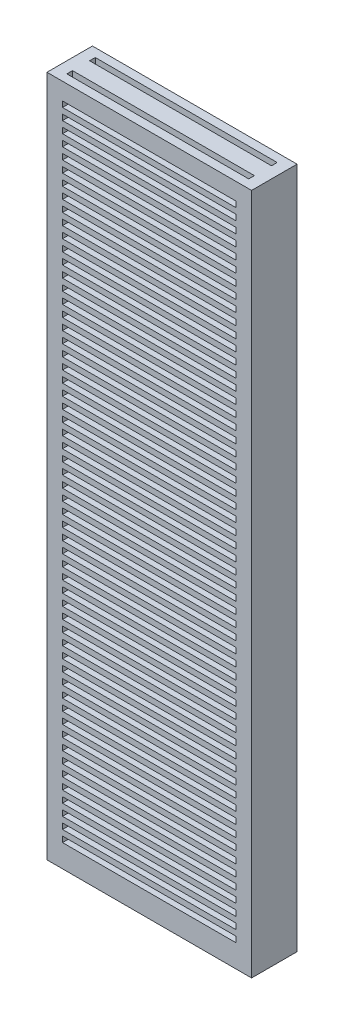
SolidWorks part; units mm, degrees
ref_plane "Front Plane" through (0, 0, 0) normal (0, 0, 1) x (1, 0, 0)
ref_plane "Top Plane" through (0, 0, 0) normal (0, 1, 0) x (1, 0, 0)
ref_plane "Right Plane" through (0, 0, 0) normal (1, 0, 0) x (0, 0, -1)
sketch "Sketch1" plane through (0, 0, 0) normal (0, 1, 0) x (1, 0, 0)
  line L1 (-4.5, -1) -> (4.5, -1)
  line L2 (-4.5, -1) -> (-4.5, 1)
  line L3 (-4.5, 1) -> (4.5, 1)
  line L4 (4.5, -1) -> (4.5, 1)
  line L5 (-4.5, -1) -> (4.5, 1) construction
  line L6 (-4.5, 1) -> (4.5, -1) construction
  point P0 (0, 0)
  dimension "D1" = 9
  dimension "D2" = 2
extrude "Boss-Extrude1" add sketch "Sketch1" along normal mid plane 30
sketch "Sketch2" plane through (0, 15, 0) normal (0, 1, 0) x (1, 0, 0)
  line L1 (-4, 0.375) -> (4, 0.375)
  line L2 (-4, 0.375) -> (-4, 0.625)
  line L3 (-4, 0.625) -> (4, 0.625)
  line L4 (4, 0.375) -> (4, 0.625)
  line L5 (-4, 0.375) -> (4, 0.625) construction
  line L6 (-4, 0.625) -> (4, 0.375) construction
  point P0 (0, 0.5)
  point P7 (0, 0)
  dimension "D1" = 0.25
  dimension "D2" = 8
  dimension "D3" = 0
  dimension "D4" = 0.5
extrude "Cut-Extrude1" cut sketch "Sketch2" against normal through all and the other way through all
mirror "Mirror1" about plane through (0, 0, 0) normal (0, 0, 1) of "Cut-Extrude1"
sketch "Sketch3" plane through (0, 0, 1) normal (0, 0, 1) x (1, 0, 0)
  line L0 (0, -1.1) -> (0, 1.1) construction
  line L1 (-3.8171, 14) -> (3.8171, 14)
  line L2 (-3.8171, 14) -> (-3.8171, 14.25)
  line L3 (-3.8171, 14.25) -> (3.8171, 14.25)
  line L4 (3.8171, 14) -> (3.8171, 14.25)
  line L5 (-3.8171, 14) -> (3.8171, 14.25) construction
  line L6 (-3.8171, 14.25) -> (3.8171, 14) construction
  line L7 (-4.5, 15) -> (4.5, 15) construction
  point P0 (0, 14.125)
  dimension "D1" = 0.25
  dimension "D2" = 0.75
extrude "Cut-Extrude2" cut sketch "Sketch3" against normal up to next
pattern_linear "LPattern1" count 57 spacing 0.5 along (0, -1, 0) of "Cut-Extrude2"
mirror "Mirror2" about plane through (0, 0, 0) normal (0, 0, 1) of "LPattern1"
